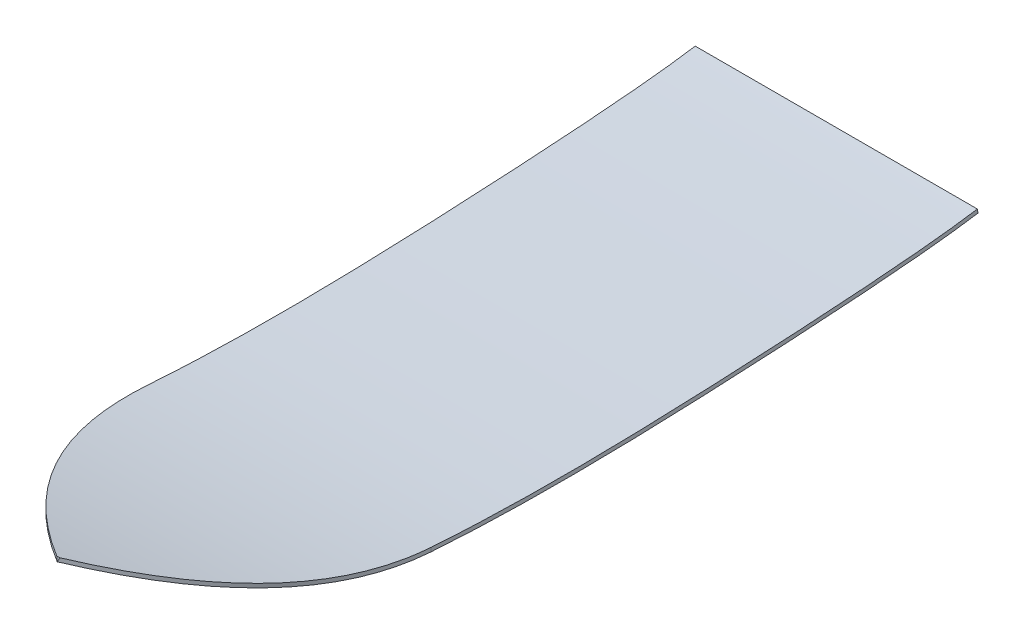
SolidWorks part; units mm, degrees
ref_plane "Front Plane" through (0, 0, 0) normal (0, 0, 1) x (1, 0, 0)
ref_plane "Top Plane" through (0, 0, 0) normal (0, 1, 0) x (1, 0, 0)
ref_plane "Right Plane" through (0, 0, 0) normal (1, 0, 0) x (0, 0, -1)
sketch "Sketch1" plane through (0, 0, 0) normal (1, 0, 0) x (0, 0, -1)
  line L22 (-2398.6114, 165.2452) -> (-2404.9447, 141.0607)
  line L23 (2565.1595, 55.295) -> (2569.1782, 30.6201)
  spline S0 degree 3 poles (-2398.6114, 165.2452) (-2303.3671, 140.3031) (-2108.5825, 93.4565) (-1814.997, 35.2118) (-1516.8074, -11.784) (-1239.7886, -44.9527) (-1055.4135, -61.3638) (-904.9512, -72.7443) (-782.389, -80.6361) (-564.0298, -91.0459) (-308.16, -98.0837) (4.9778, -99.4443) (325.9332, -94.6157) (656.4804, -84.4468) (902.2793, -73.886) (1042.5573, -67.1294) (1071.8154, -65.695) (1170.7291, -60.8067) (1384.2693, -49.554) (1709.6271, -29.5823) (2155.7877, 3.842) (2431.9381, 33.5977) (2565.1595, 55.295) knots 0.003044 0.003044 0.003044 0.003044 0.0625 0.125 0.1875 0.25 0.298828 0.302734 0.34375 0.375 0.4375 0.5 0.5625 0.625 0.6875 0.697266 0.700195 0.703125 0.75 0.8125 0.875 1 1 1 1
  spline S1 degree 1 poles (-2404.9447, 141.0607) (2569.1782, 30.6201) knots 0 0 1 1 construction
  spline S2 degree 3 poles (-2404.9447, 141.0607) (-2392.4389, 137.7858) (-2367.3913, 131.2963) (-2317.3808, 118.6175) (-2254.9159, 103.2997) (-2180.0558, 85.7631) (-2080.3433, 63.4867) (-1955.8667, 37.6827) (-1806.6556, 9.8688) (-1657.5064, -14.9095) (-1458.584, -44.0647) (-1209.5679, -73.5377) (-959.49, -94.5726) (-758.2294, -106.8785) (-555.7642, -116.3545) (-300.0293, -123.2035) (12.8649, -124.3915) (280.0421, -120.2654) (498.525, -114.3175) (664.9863, -108.6345) (834.2768, -101.8308) (977.9211, -95.3097) (1094.5123, -89.6318) (1212.1027, -83.6619) (1360.214, -75.6558) (1537.4602, -65.1956) (1711.9298, -53.9) (1881.3388, -41.7865) (2016.3782, -31.025) (2119.5815, -22.0239) (2194.284, -15.0793) (2266.0012, -7.9427) (2334.4493, -0.6157) (2388.5298, 5.6478) (2429.8787, 10.7531) (2459.8981, 14.6293) (2488.8907, 18.5529) (2512.1676, 21.8624) (2530.2415, 24.5339) (2543.5208, 26.5499) (2554.3469, 28.2393) (2562.8765, 29.5988) (2567.0723, 30.2771) (2569.1782, 30.6201) knots 0.003044 0.003044 0.003044 0.003044 0.010832 0.018621 0.034199 0.049776 0.065353 0.096508 0.127663 0.158818 0.189973 0.252283 0.314592 0.345747 0.376902 0.439212 0.501522 0.563832 0.594986 0.626141 0.657296 0.688451 0.704029 0.719606 0.750761 0.781916 0.813071 0.844226 0.87538 0.890958 0.906535 0.922113 0.93769 0.953268 0.961056 0.968845 0.976634 0.984423 0.988317 0.992211 0.996106 0.998053 1 1 1 1
  dimension "D1" = 25
extrude "Boss-Extrude1" add sketch "Sketch1" along normal blind 1524 and the other way blind 1524
sketch "Sketch3" plane through (0, 0, 0) normal (0, 1, 0) x (1, 0, 0)
  line L0 (-900, 2596.4146) -> (900, 2596.4146)
  line L1 (-900, 2596.4146) -> (-900, -921.119)
  line L2 (900, 2596.4146) -> (900, -921.119)
  line L3 (0, 2955.5244) -> (0, -2061.9995) construction
  line L4 (-2934.2017, 5372.0277) -> (2797.2556, 5372.0277)
  line L5 (-2934.2017, 5372.0277) -> (-2934.2017, -2631.2782)
  line L6 (-2934.2017, -2631.2782) -> (2797.2556, -2631.2782)
  line L7 (2797.2556, 5372.0277) -> (2797.2556, -2631.2782)
  line L8 (-94.9374, 0) -> (0, 0) construction
  line L10 (-1524, -2404.9447) -> (1524, -2404.9447) construction
  line L11 (-1524, 1954.9582) -> (1524, 1954.9582) construction
  spline S0 degree 2 poles (-900, -921.119) (-900, -1795.7576) (0, -2404.9447) knots 0 0 0 1 1 1
  spline S1 degree 2 poles (900, -921.119) (900, -1795.7576) (0, -2404.9447) knots 0 0 0 1 1 1
  point P13 (0, -2404.9447)
  dimension "D1" = 1800
extrude "Cut-Extrude1" cut sketch "Sketch3" against normal through all both and the other way through all
